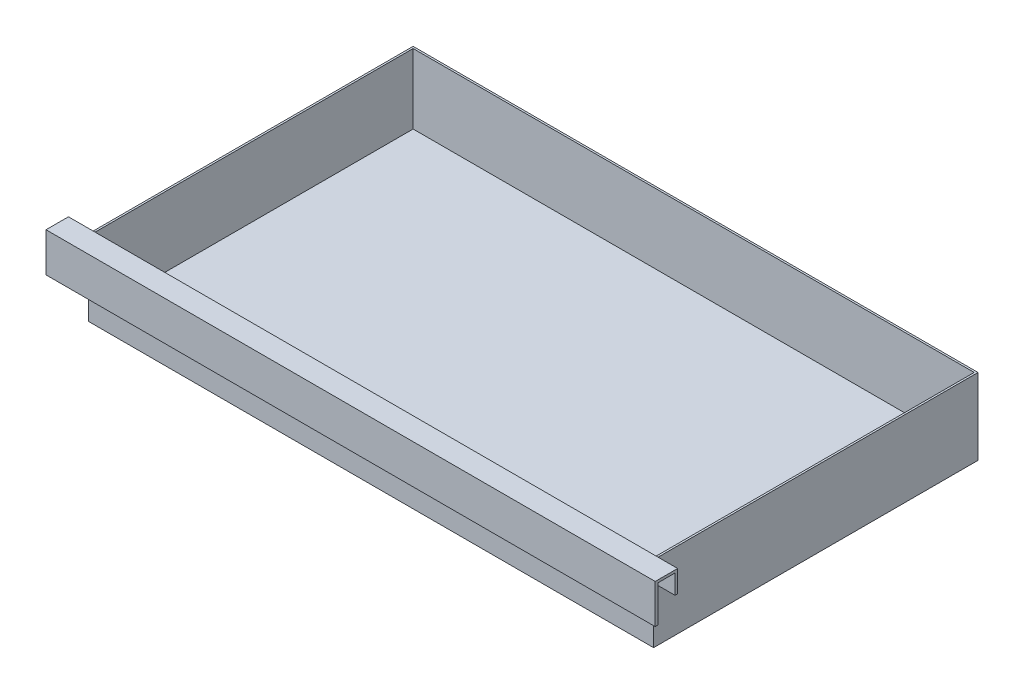
SolidWorks part; units mm, degrees
material "AISI 4130 Steel, normalized at 870C"
ref_plane "Front Plane" through (0, 0, 0) normal (0, 0, 1) x (1, 0, 0)
ref_plane "Top Plane" through (0, 0, 0) normal (0, 1, 0) x (1, 0, 0)
ref_plane "Right Plane" through (0, 0, 0) normal (1, 0, 0) x (0, 0, -1)
sketch "Sketch1" plane through (0, 0, 0) normal (0, 1, 0) x (1, 0, 0)
  line L0 (-111.125, 0) -> (111.125, 0)
  line L1 (111.125, 0) -> (111.125, 127)
  line L2 (111.125, 127) -> (-111.125, 127)
  line L3 (-111.125, 127) -> (-111.125, 0)
  line L4 (-111.8743, 127.7493) -> (-111.8743, -0.7493)
  line L5 (-111.8743, -0.7493) -> (111.8743, -0.7493)
  line L6 (111.8743, -0.7493) -> (111.8743, 127.7493)
  line L7 (111.8743, 127.7493) -> (-111.8743, 127.7493)
  point P9 (0, 0)
  dimension "D2" = 127
  dimension "D3" = 222.25
  dimension "D1" = 0.7493
extrude "Base" add sketch "Sketch1" along normal blind 2.54 contours L2 L3 L0 L1 | L6 L7 L4 L5 L3 L2 L1 L0 region at (0, 0, -63.5) region at (0, 0, -127.4913)
extrude "Walls" add sketch "Sketch1<3>" along normal blind 30.1625
sketch "Sketch1<3>" plane through (0, 0, 0) normal (0, 1, 0) x (1, 0, 0) same geometry as "Sketch1"
sketch "Sketch2" plane through (0, 0, 0) normal (1, 0, 0) x (0, 0, -1)
  line L2 (0, 22.4754) -> (0, 31.1785)
  line L3 (0, 31.1785) -> (-8.89, 31.1785)
  line L4 (-8.89, 31.1785) -> (-8.89, 15.6845)
  line L9 (-1.016, 22.4754) -> (-1.016, 30.1625)
  line L10 (-1.016, 30.1625) -> (-7.874, 30.1625)
  line L11 (-7.874, 30.1625) -> (-7.874, 15.6845)
  line L12 (-8.89, 15.6845) -> (-7.874, 15.6845)
  line L13 (-1.016, 22.4754) -> (0, 22.4754)
  line L14 (-0.7493, 30.1625) -> (127.7493, 30.1625) construction
  dimension "D1" = 1.016
  dimension "D2" = 8.89
  dimension "D3" = 15.494
  dimension "D4" = 8.7031
extrude "Handle" add sketch "Sketch2" along normal blind 120.65 and the other way blind 120.65
